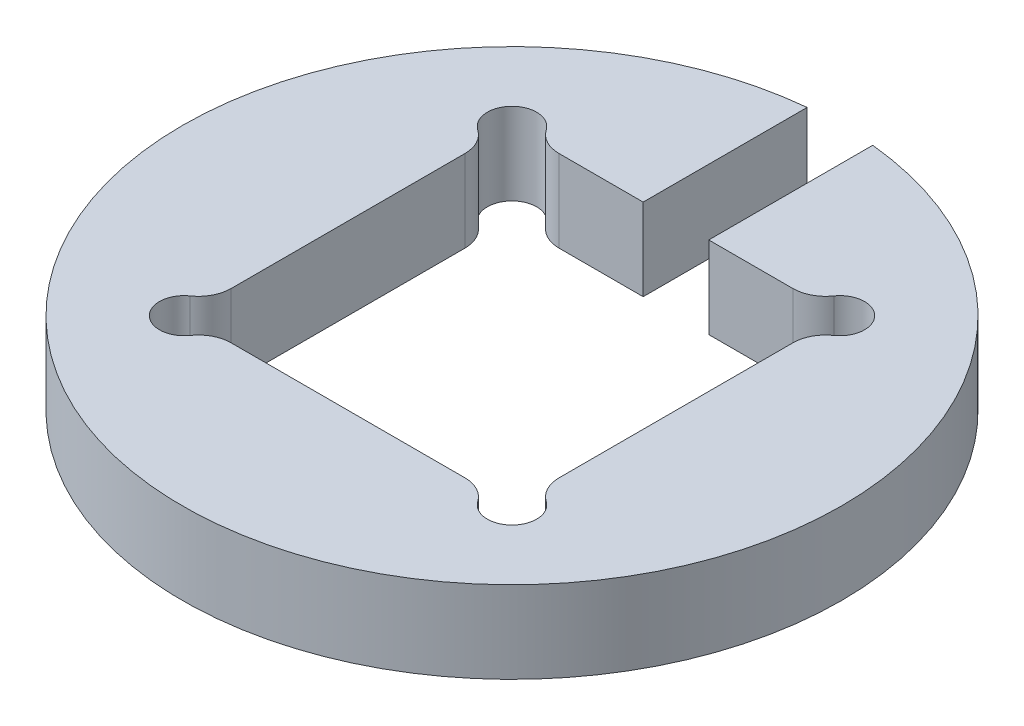
SolidWorks part; units mm, degrees
ref_plane "Front Plane" through (0, 0, 0) normal (0, 0, 1) x (1, 0, 0)
ref_plane "Top Plane" through (0, 0, 0) normal (0, 1, 0) x (1, 0, 0)
ref_plane "Right Plane" through (0, 0, 0) normal (1, 0, 0) x (0, 0, -1)
sketch "Sketch1" plane through (0, 0, 0) normal (0, 1, 0) x (1, 0, 0)
  line L0 (0, 0) -> (0, 20)
  line L1 (0, 20) -> (8, 20)
  line L2 (8, 20) -> (8, 30)
  line L3 (0, 0) -> (20, 0)
  line L4 (20, 0) -> (20, 20)
  line L5 (20, 20) -> (12, 20)
  line L6 (12, 20) -> (12, 30)
  line L7 (0, 10) -> (20, 10) construction
  arc A2 (12, 30) -> (8, 30) centre (10, 10) cw
  arc A3 (18.5, 20) -> (20, 18.5) centre (20, 20) cw
  arc A4 (20, 1.5) -> (18.5, 0) centre (20, 0) cw
  arc A5 (1.5, 0) -> (0, 1.5) centre (0, 0) cw
  arc A6 (1.5, 20) -> (0, 18.5) centre (0, 20) ccw
  dimension "D1" = 20
  dimension "D7" = 1.5
  dimension "D5" = 1.5
  dimension "D8" = 1.5
  dimension "D9" = 1.5
  dimension "D2" = 20
  dimension "D3" = 4
  dimension "D4" = 10
extrude "Boss-Extrude1" add sketch "Sketch1" along normal blind 5 contours A6 L1 L2 A2 L6 L5 A3 L4 A4 L3 A5 L0 region at (-1.4622, 0, 1.4622)
fillet "Fillet1" radius 2 8 edges at (18.5, 2.5, 0) (20, 2.5, -1.5) (20, 2.5, -18.5) (0, 2.5, -1.5) (1.5, 2.5, 0) (0, 2.5, -18.5) (18.5, 2.5, -20) (1.5, 2.5, -20)
